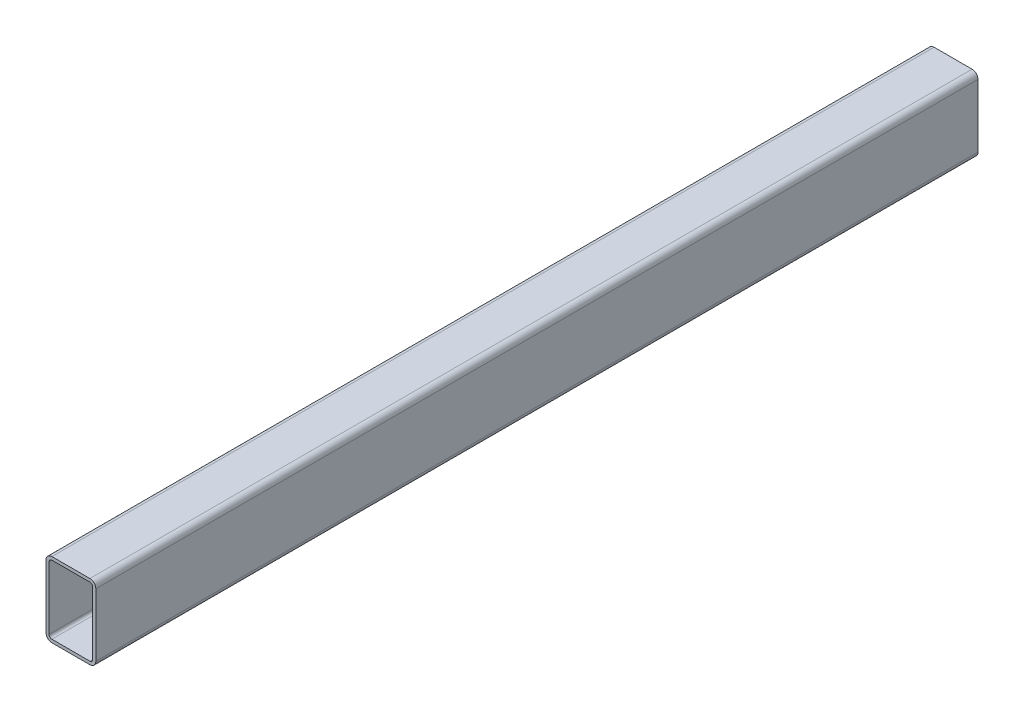
SolidWorks part; units mm, degrees
ref_plane "Front Plane" through (0, 0, 0) normal (0, 0, 1) x (1, 0, 0)
ref_plane "Top Plane" through (0, 0, 0) normal (0, 1, 0) x (1, 0, 0)
ref_plane "Right Plane" through (0, 0, 0) normal (1, 0, 0) x (0, 0, -1)
sketch "Sketch1" plane through (0, 0, 0) normal (0, 0, 1) x (1, 0, 0)
  line L0 (19.4, 34.925) -> (-19.4, 34.925)
  line L1 (19.4, -38.1) -> (-19.4, -38.1)
  line L2 (25.4, -32.1) -> (25.4, 32.1)
  line L3 (19.4, 38.1) -> (-19.4, 38.1)
  line L4 (-25.4, -32.1) -> (-25.4, 32.1)
  line L5 (25.4, -38.1) -> (-25.4, 38.1) construction
  line L6 (25.4, 38.1) -> (-25.4, -38.1) construction
  line L7 (-22.225, -32.1) -> (-22.225, 32.1)
  line L8 (19.4, -34.925) -> (-19.4, -34.925)
  line L9 (22.225, -32.1) -> (22.225, 32.1)
  arc A0 (-19.4, -38.1) -> (-25.4, -32.1) centre (-19.4, -32.1) cw
  arc A1 (19.4, -38.1) -> (25.4, -32.1) centre (19.4, -32.1) ccw
  arc A2 (25.4, 32.1) -> (19.4, 38.1) centre (19.4, 32.1) ccw
  arc A3 (-19.4, 38.1) -> (-25.4, 32.1) centre (-19.4, 32.1) ccw
  arc A4 (-19.4, 34.925) -> (-22.225, 32.1) centre (-19.4, 32.1) ccw
  arc A5 (-19.4, -34.925) -> (-22.225, -32.1) centre (-19.4, -32.1) cw
  arc A6 (19.4, -34.925) -> (22.225, -32.1) centre (19.4, -32.1) ccw
  arc A7 (22.225, 32.1) -> (19.4, 34.925) centre (19.4, 32.1) ccw
  point P0 (0, 0)
  dimension "D1" = 6
  dimension "D3" = 76.2
  dimension "D4" = 50.8
  dimension "D2" = 3.175
extrude "Boss-Extrude1" add sketch "Sketch1" along normal mid plane 900
equation "\"M5_tap\"=4.2mm       ' Below you can do mesurements as follows: cm, mm, ft, in, m, "
equation "\"M5_clearence\"=5.5mm"
equation "\"M6_tap\"=5mm"
equation "\"M6_clearence\"=6.6mm"
equation "\"work_area_width\"=1100mm"
equation "\"work_area_depth\"=900mm"
equation "\"D3@Sketch1\"=\"steel_sides_width\""
equation "\"D4@Sketch1\"=\"steel_sides_height\""
equation "\"D1@Sketch1\"=\"steel_sides_radius\""
equation "\"D2@Sketch1\"=\"steel_sides_wall_thickness\""
equation "\"D1@Boss-Extrude1\"=\"work_area_depth\""
equation "\"steel_base_width\"=3in "
equation "\"steel_base_height\"=2in"
equation "\"steel_base_wall_thickness\"=0.125in"
equation "\"steel_base_radius\"=6mm"
equation "\"steel_sides_width\"=3in     'this tube is rotated so flip width/height"
equation "\"steel_sides_height\"=2in    'this tube is rotated so flip width/height"
equation "\"steel_sides_wall_thickness\"=0.125in"
equation "\"steel_sides_radius\"=6mm"
equation "\"steel_gantry_width\"=4in    'this tube is rotated so flip width/height"
equation "\"steel_gantry_height\"=3in    'this tube is rotated so flip width/height"
equation "\"steel_gantry_wall_thickness\"=0.125in"
equation "\"steel_gantry_radius\"=6mm"
equation "\"steel_rollers_width\"=3in"
equation "\"steel_rollers_height\"=2in    'keep as low as possible as this increases how big plastic parts are"
equation "\"steel_rollers_wall_thickness\"=0.125in"
equation "\"steel_rollers_radius\"=6mm"
equation "\"steel_zbox_width\"=4in     'if the gantry height (rotated) is too thick, a wider zbox is necessary"
equation "\"steel_zbox_height\"=2in     'hole patteren changes as the zbox and gantry height (rotated) changes."
equation "\"steel_zbox_wall_thickness\"=0.125in"
equation "\"steel_zbox_radius\"=6mm"
equation "\"alu_zangle_width\"=3.5in     'check that it doesn't interfer with the gantry"
equation "\"alu_zangle_height\"=2in"
equation "\"alu_zangle_wall_thickness\"=0.25in   'check that it doesn't interfer with the gantry"
